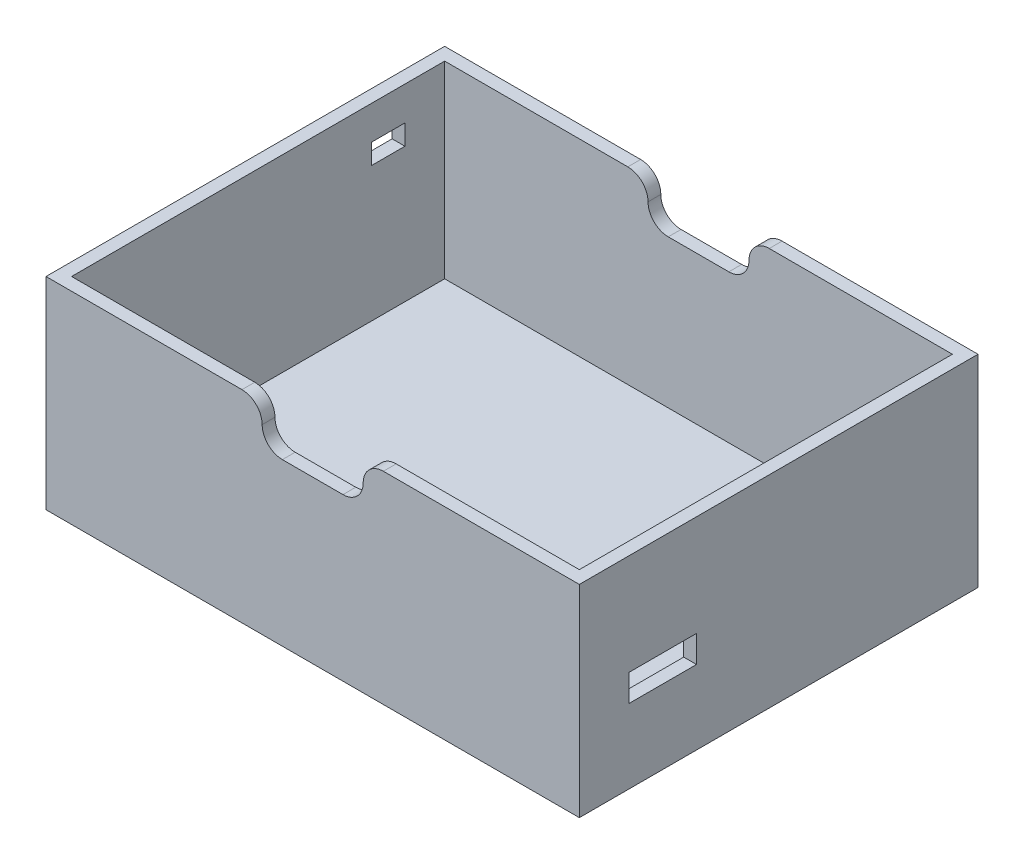
SolidWorks part; units mm, degrees
ref_plane "Front Plane" through (0, 0, 0) normal (0, 0, 1) x (1, 0, 0)
ref_plane "Top Plane" through (0, 0, 0) normal (0, 1, 0) x (1, 0, 0)
ref_plane "Right Plane" through (0, 0, 0) normal (1, 0, 0) x (0, 0, -1)
sketch "Sketch1" plane through (0, 0, 0) normal (0, 1, 0) x (1, 0, 0)
  line L1 (0, 0) -> (100.584, 0)
  line L2 (0, 0) -> (0, 75.184)
  line L3 (0, 75.184) -> (100.584, 75.184)
  line L4 (100.584, 0) -> (100.584, 75.184)
  dimension "D1" = 75.184
  dimension "D2" = 100.584
extrude "Boss-Extrude1" add sketch "Sketch1" along normal blind 2.54
sketch "Sketch2" plane through (0, 2.54, 0) normal (0, 1, 0) x (1, 0, 0)
  line L1 (0, 75.184) -> (100.584, 75.184)
  line L2 (0, 75.184) -> (0, 0)
  line L3 (0, 0) -> (100.584, 0)
  line L4 (100.584, 75.184) -> (100.584, 0)
  line L5 (2.413, 72.771) -> (98.171, 72.771)
  line L6 (2.413, 72.771) -> (2.413, 2.413)
  line L7 (2.413, 2.413) -> (98.171, 2.413)
  line L8 (98.171, 72.771) -> (98.171, 2.413)
  point P10 (0, 37.592)
  point P11 (50.292, 75.184)
  point P12 (50.292, 72.771)
  point P13 (0, 0)
  point P14 (2.413, 37.592)
  dimension "D1" = 70.358
  dimension "D2" = 95.758
extrude "Boss-Extrude2" add sketch "Sketch2" along normal blind 35.56
sketch "Sketch3" plane through (0, 0, -75.184) normal (0, 0, -1) x (-1, 0, 0)
  line L0 (-100.584, 38.1) -> (0, 38.1) construction
  line L1 (-59.817, 38.1) -> (-40.767, 38.1)
  line L2 (-59.817, 38.1) -> (-59.817, 30.48)
  line L3 (-59.817, 30.48) -> (-40.767, 30.48)
  line L4 (-40.767, 38.1) -> (-40.767, 30.48)
  line L5 (-100.584, 0) -> (0, 0) construction
  point P6 (-50.292, 30.48)
  point P7 (-50.292, 0)
  point P8 (0, 0)
  dimension "D1" = 19.05
  dimension "D2" = 7.62
extrude "Cut-Extrude1" cut sketch "Sketch3" against normal through all
fillet "Fillet1" radius 3.81 8 edges at (40.767, 30.48, -1.2065) (59.817, 30.48, -1.2065) (59.817, 30.48, -73.9775) (40.767, 30.48, -73.9775) (40.767, 38.1, -1.2065) (59.817, 38.1, -1.2065) (59.817, 38.1, -73.9775) (40.767, 38.1, -73.9775)
sketch "Sketch4" plane through (0, 0, 0) normal (-1, 0, 0) x (0, 0, 1)
  line L0 (-75.184, 38.1) -> (0, 38.1) construction
  line L1 (-58.928, 38.1) -> (-65.278, 38.1)
  line L2 (-58.928, 31.7503) -> (-58.928, 27.9403)
  line L3 (-58.928, 27.9403) -> (-65.278, 27.9403)
  line L4 (-65.278, 31.7503) -> (-65.278, 27.9403)
  line L5 (-65.278, 31.7503) -> (-58.928, 31.7503)
extrude "Cut-Extrude2" cut sketch "Sketch4" against normal blind 6.35 contours L5 L4 L3 L2 region at (0, 29.8453, -62.103)
sketch "Sketch5" plane through (100.584, 0, 0) normal (1, 0, 0) x (0, 0, -1)
  line L1 (22.098, 13.9703) -> (9.398, 13.9703)
  line L2 (22.098, 13.9703) -> (22.098, 19.0503)
  line L3 (22.098, 19.0503) -> (9.398, 19.0503)
  line L4 (9.398, 13.9703) -> (9.398, 19.0503)
extrude "Cut-Extrude3" cut sketch "Sketch5" against normal blind 6.35
